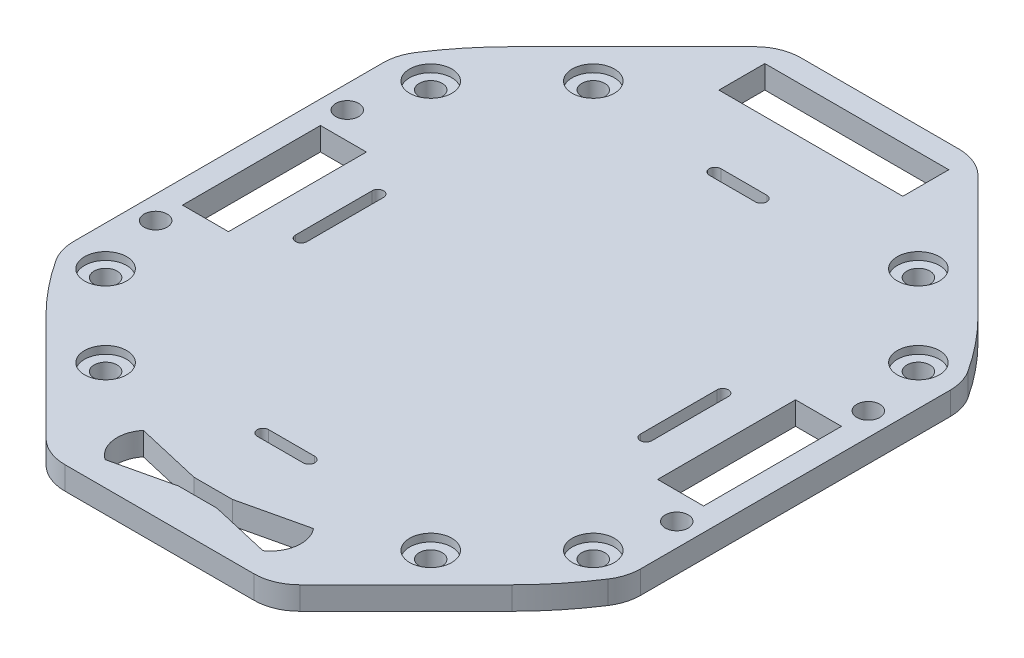
SolidWorks part; units mm, degrees
ref_plane "前视基准面" through (0, 0, 0) normal (0, 0, 1) x (1, 0, 0)
ref_plane "上视基准面" through (0, 0, 0) normal (0, 1, 0) x (1, 0, 0)
ref_plane "右视基准面" through (0, 0, 0) normal (1, 0, 0) x (0, 0, -1)
sketch "草图1" plane through (0, 0, 0) normal (0, 1, 0) x (1, 0, 0)
  line L0 (0, 0) -> (0, 70.7992) construction
  line L1 (0, 0) -> (104.9803, 0) construction
  line L2 (0, 0) -> (-64.2109, 64.2109) construction
  line L3 (-9.176, 43.857) -> (-46.4815, 6.5515) construction
  line L4 (-33.5876, 15.9099) -> (-15.9099, 33.5876) construction
  line L5 (-10.3259, 48) -> (10.3259, 48)
  line L6 (-37, 20.199) -> (-37, -20.199)
  line L7 (-10.3259, -48) -> (10.3259, -48)
  line L8 (37, 20.199) -> (37, -20.199)
  line L11 (-37.1231, 19.4454) -> (-19.4454, 37.1231) construction
  line L12 (-39.2444, 21.5668) -> (-21.5668, 39.2444) construction
  line L13 (-30.4056, 30.4056) -> (-14.5685, 46.2426)
  line L14 (30.4056, 30.4056) -> (14.5685, 46.2426)
  line L15 (-30.4056, -30.4056) -> (-14.5685, -46.2426)
  line L16 (30.4056, -30.4056) -> (14.5685, -46.2426)
  circle A0 centre (-21.2132, 31.8198) radius 1.5
  circle A1 centre (-31.8198, 21.2132) radius 1.5
  circle A2 centre (31.8198, 21.2132) radius 1.5
  circle A3 centre (21.2132, 31.8198) radius 1.5
  circle A4 centre (-31.8198, -21.2132) radius 1.5
  circle A5 centre (-21.2132, -31.8198) radius 1.5
  circle A6 centre (31.8198, -21.2132) radius 1.5
  circle A7 centre (21.2132, -31.8198) radius 1.5
  arc A8 (-37, 20.199) -> (-36.027, 23.4745) centre (-31, 20.199) cw
  arc A9 (-30.4056, 30.4056) -> (-36.027, 23.4745) centre (0, 0) ccw
  arc A10 (-10.3259, 48) -> (-14.5685, 46.2426) centre (-10.3259, 42) ccw
  arc A11 (10.3259, 48) -> (14.5685, 46.2426) centre (10.3259, 42) cw
  arc A12 (30.4056, 30.4056) -> (36.027, 23.4745) centre (0, 0) cw
  arc A13 (37, 20.199) -> (36.027, 23.4745) centre (31, 20.199) ccw
  arc A14 (-10.3259, -48) -> (-14.5685, -46.2426) centre (-10.3259, -42) cw
  arc A15 (-30.4056, -30.4056) -> (-36.027, -23.4745) centre (0, 0) cw
  arc A16 (-37, -20.199) -> (-36.027, -23.4745) centre (-31, -20.199) ccw
  arc A17 (10.3259, -48) -> (14.5685, -46.2426) centre (10.3259, -42) ccw
  arc A18 (30.4056, -30.4056) -> (36.027, -23.4745) centre (0, 0) ccw
  arc A19 (37, -20.199) -> (36.027, -23.4745) centre (31, -20.199) cw
  dimension "D3" = 3
  dimension "D17" = 6
  dimension "D19" = 6
  dimension "D1" = 45
  dimension "D2" = 37.5
  dimension "D4" = 15
  dimension "D5" = 7.5
  dimension "D6" = 20.6518
  dimension "D7" = 74
  dimension "D8" = 2.5
  dimension "D9" = 2.5
  dimension "D10" = 25
  dimension "D11" = 12.5
  dimension "D12" = 25
  dimension "D13" = 12.5
  dimension "D14" = 8
  dimension "D15" = 25
  dimension "D16" = 12.5
  dimension "D18" = 36.027
extrude "凸台-拉伸1" add sketch "草图1" along normal blind 3
sketch "草图2" plane through (0, 3, 0) normal (0, 1, 0) x (1, 0, 0)
  circle A0 centre (-21.2132, 31.8198) radius 2.75
  circle A1 centre (-31.8198, 21.2132) radius 2.75
  circle A2 centre (21.2132, 31.8198) radius 2.75
  circle A3 centre (31.8198, 21.2132) radius 2.75
  circle A4 centre (-31.8198, -21.2132) radius 2.75
  circle A5 centre (-21.2132, -31.8198) radius 2.75
  circle A7 centre (21.2132, -31.8198) radius 2.75
  circle A8 centre (31.8198, -21.2132) radius 2.75
  dimension "D1" = 5.5
extrude "切除-拉伸1" cut sketch "草图2" against normal blind 1
sketch "草图3" plane through (0, 3, 0) normal (0, 1, 0) x (1, 0, 0)
  line L0 (-10.3259, -48) -> (10.3259, -48) construction
  line L1 (-12, -37) -> (12, -37)
  line L2 (-12, -37) -> (-12, -43)
  line L3 (-12, -43) -> (12, -43)
  line L4 (12, -37) -> (12, -43)
  line L5 (-12, -37) -> (12, -43) construction
  line L6 (-12, -43) -> (12, -37) construction
  line L7 (10.3259, 48) -> (-10.3259, 48) construction
  line L8 (-12, 45) -> (12, 45)
  line L9 (-12, 45) -> (-12, 39)
  line L10 (-12, 39) -> (12, 39)
  line L11 (12, 45) -> (12, 39)
  line L12 (-12, 45) -> (12, 39) construction
  line L13 (-12, 39) -> (12, 45) construction
  line L14 (-37, 20.199) -> (-37, -20.199) construction
  line L15 (37, -20.199) -> (37, 20.199) construction
  line L16 (0, 0) -> (45.415, 0) construction
  line L17 (0, 0) -> (0, 53.3677) construction
  line L18 (34, -9) -> (28, -9)
  line L19 (-34, 9) -> (-28, 9)
  line L20 (-34, 9) -> (-34, -9)
  line L21 (-34, -9) -> (-28, -9)
  line L22 (-28, 9) -> (-28, -9)
  line L23 (-34, 9) -> (-28, -9) construction
  line L24 (-34, -9) -> (-28, 9) construction
  line L25 (28, 9) -> (28, -9)
  line L26 (34, 9) -> (28, 9)
  line L27 (34, 9) -> (34, -9)
  circle A0 centre (-34, 12.5) radius 1.5
  circle A1 centre (-34, -12.5) radius 1.5
  circle A2 centre (34, 12.5) radius 1.5
  circle A3 centre (34, -12.5) radius 1.5
  point P0 (0, -40)
  point P9 (0, 42)
  point P25 (-31, 0)
  dimension "D7" = 3
  dimension "D1" = 6
  dimension "D2" = 24
  dimension "D3" = 5
  dimension "D4" = 24
  dimension "D5" = 6
  dimension "D6" = 3
  dimension "D8" = 3
  dimension "D9" = 3
  dimension "D10" = 25
  dimension "D11" = 12.5
  dimension "D12" = 6
  dimension "D13" = 18
  dimension "D14" = 3
extrude "切除-拉伸2" cut sketch "草图3" against normal blind 10
sketch "草图4" plane through (0, 0, 0) normal (0, -1, 0) x (1, 0, 0)
  line L0 (0, 0) -> (0, 54.2429) construction
  line L1 (-8, 46) -> (8, 46) construction
  line L2 (-10.3259, 48) -> (10.3259, 48) construction
  line L3 (-10.3259, 48) -> (10.3259, 48) construction
  line L4 (10.3259, 48) -> (10.3259, 49) construction
  line L5 (10.3259, 49) -> (-10.3259, 49) construction
  line L6 (-10.3259, 49) -> (-10.3259, 48) construction
  line L7 (-12.3259, 46) -> (12.3259, 46)
  line L8 (14.5685, 46.2426) -> (30.4056, 30.4056) construction
  line L9 (-30.4056, 30.4056) -> (-14.5685, 46.2426) construction
  line L10 (16.5685, 44.2426) -> (30.4056, 30.4056) construction
  line L11 (-30.4056, 30.4056) -> (-16.5685, 44.2426) construction
  line L12 (-16.5685, 44.2426) -> (-16.5685, 49)
  line L13 (-16.5685, 49) -> (16.5685, 49)
  line L14 (16.5685, 49) -> (16.5685, 44.2426)
  arc A0 (-10.3259, 48) -> (-14.5685, 46.2426) centre (-10.3259, 42) ccw construction
  arc A1 (-10.3259, 48) -> (-14.5685, 46.2426) centre (-10.3259, 42) ccw construction
  arc A2 (14.5685, 46.2426) -> (10.3259, 48) centre (10.3259, 42) ccw construction
  arc A3 (14.5685, 46.2426) -> (10.3259, 48) centre (10.3259, 42) ccw construction
  arc A4 (10.3259, 48) -> (9, 46.8599) centre (10.3259, 46.659) ccw construction
  arc A5 (9, 46.8599) -> (8, 46) centre (8, 47.0114) cw construction
  arc A6 (-9, 46.8599) -> (-8, 46) centre (-8, 47.0114) ccw construction
  arc A7 (-10.3259, 48) -> (-9, 46.8599) centre (-10.3259, 46.659) cw construction
  arc A8 (16.5685, 44.2426) -> (12.3259, 46) centre (12.3259, 40) ccw
  arc A9 (-12.3259, 46) -> (-16.5685, 44.2426) centre (-12.3259, 40) ccw
  dimension "D5" = 6
  dimension "D1" = 2
  dimension "D2" = 16
  dimension "D3" = 1
  dimension "D4" = 18
  dimension "D6" = 3
extrude "切除-拉伸3" cut sketch "草图4" against normal blind 10
sketch "草图5" plane through (0, 0, 0) normal (0, -1, 0) x (1, 0, 0)
  line L0 (-12, 37) -> (12, 37) construction
  line L1 (12, 37) -> (12, 43) construction
  line L2 (-12, 43) -> (-12, 37) construction
  line L3 (12, 43) -> (-12, 43) construction
  line L4 (-12, 37) -> (12, 37) construction
  line L5 (12, 37) -> (12, 43) construction
  line L6 (-12, 43) -> (-12, 37) construction
  line L7 (12, 43) -> (-12, 43) construction
  line L8 (-10.3, 42.8081) -> (-2.5, 41)
  line L9 (-2.5, 41) -> (2.5, 41)
  line L10 (2.5, 41) -> (10.3, 42.8081)
  line L11 (-12, 40) -> (12, 40) construction
  line L12 (0, 43) -> (0, 37) construction
  line L13 (2.5, 39) -> (11.1, 37.0076)
  line L14 (-2.5, 39) -> (2.5, 39)
  line L15 (-11.1, 37.0076) -> (-2.5, 39)
  line L16 (-12, 37) -> (-12, 36)
  line L17 (-12, 36) -> (12, 36)
  line L18 (12, 36) -> (12, 37)
  line L19 (-12, 43) -> (-12, 44)
  line L20 (-12, 44) -> (12, 44)
  line L21 (12, 44) -> (12, 43)
  line L22 (-12, 43) -> (-13, 43)
  line L24 (-13, 43) -> (-13, 37)
  line L25 (-13, 37) -> (-12, 37)
  line L26 (12, 43) -> (13, 43)
  line L27 (13, 43) -> (13, 37)
  line L28 (13, 37) -> (12, 37)
  arc A0 (-10.3, 42.8081) -> (-11.1, 37.0076) centre (-8, 39.5355) ccw
  arc A1 (10.3, 42.8081) -> (11.1, 37.0076) centre (8, 39.5355) cw
  dimension "D6" = 4
  dimension "D2" = 5
  dimension "D3" = 2.5
  dimension "D4" = 1
  dimension "D5" = 1
  dimension "D7" = 7.8
  dimension "D8" = 2.8081
  dimension "D9" = 8.6
  dimension "D10" = 7.8
  dimension "D11" = 8.6
  dimension "D12" = 1
  dimension "D13" = 1
  dimension "D14" = 2
extrude "凸台-拉伸2" add sketch "草图5" against normal blind 3
sketch "草图6" plane through (0, 0, 0) normal (0, -1, 0) x (1, 0, 0)
  line L0 (-22.5, 5) -> (-22.5, -5) construction
  line L1 (-19.5, 26.5) -> (19.5, 26.5) construction
  line L2 (-19.5, 26.5) -> (-19.5, -26.5) construction
  line L3 (-19.5, -26.5) -> (19.5, -26.5) construction
  line L4 (19.5, 26.5) -> (19.5, -26.5) construction
  line L5 (-19.5, 26.5) -> (19.5, -26.5) construction
  line L6 (-19.5, -26.5) -> (19.5, 26.5) construction
  line L11 (-21.75, 5) -> (-21.75, -5)
  line L12 (-23.25, 5) -> (-23.25, -5)
  line L13 (-3, 29.5) -> (3, 29.5) construction
  line L14 (-3, 30.25) -> (3, 30.25)
  line L15 (-3, 28.75) -> (3, 28.75)
  line L16 (0, 0) -> (0, 15.348) construction
  line L17 (0, 0) -> (11.1231, 0) construction
  line L18 (-3, -29.5) -> (3, -29.5) construction
  line L19 (-3, -30.25) -> (3, -30.25)
  line L20 (-3, -28.75) -> (3, -28.75)
  line L21 (22.5, 5) -> (22.5, -5) construction
  line L22 (21.75, 5) -> (21.75, -5)
  line L23 (23.25, 5) -> (23.25, -5)
  arc A0 (-21.75, 5) -> (-23.25, 5) centre (-22.5, 5) ccw
  arc A1 (-23.25, -5) -> (-21.75, -5) centre (-22.5, -5) ccw
  arc A2 (-3, 30.25) -> (-3, 28.75) centre (-3, 29.5) ccw
  arc A3 (3, 28.75) -> (3, 30.25) centre (3, 29.5) ccw
  arc A4 (-3, -30.25) -> (-3, -28.75) centre (-3, -29.5) cw
  arc A5 (3, -28.75) -> (3, -30.25) centre (3, -29.5) cw
  arc A6 (21.75, 5) -> (23.25, 5) centre (22.5, 5) cw
  arc A7 (23.25, -5) -> (21.75, -5) centre (22.5, -5) cw
  point P0 (0, 0)
  point P8 (-22.5, 0)
  point P13 (0, 29.5)
  point P22 (0, 0)
  point P24 (0, 0)
  point P25 (0, 0)
  point P26 (0, 0)
  point P27 (0, 0)
  point P28 (0, 0)
  point P29 (0, 0)
  point P30 (0, 0)
  point P33 (0, -29.5)
  point P40 (22.5, 0)
  dimension "D1" = 39
  dimension "D2" = 53
  dimension "D3" = 1.5
  dimension "D4" = 1.5
  dimension "D5" = 10
  dimension "D6" = 6
  dimension "D7" = 3
  dimension "D8" = 3
extrude "切除-拉伸4" cut sketch "草图6" against normal blind 3
